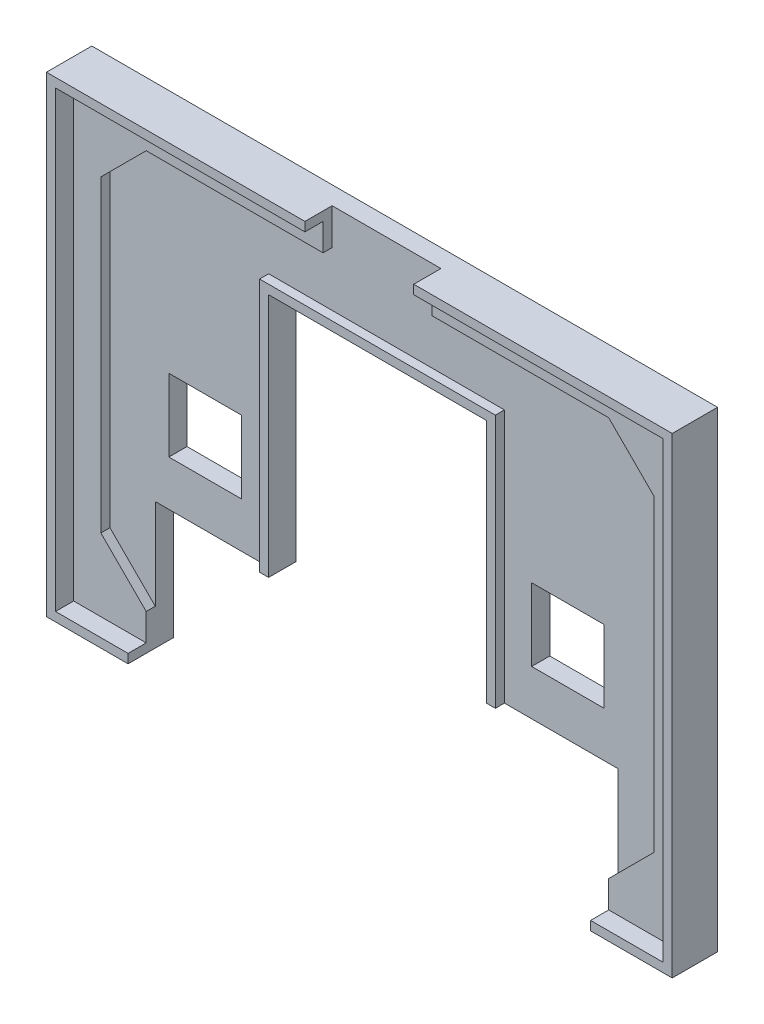
SolidWorks part; units mm, degrees
ref_plane "Přední rovina" through (0, 0, 0) normal (0, 0, 1) x (1, 0, 0)
ref_plane "Horní rovina" through (0, 0, 0) normal (0, 1, 0) x (1, 0, 0)
ref_plane "Pravá rovina" through (0, 0, 0) normal (1, 0, 0) x (0, 0, -1)
sketch "Skica1" plane through (0, 0, 0) normal (0, 0, 1) x (1, 0, 0)
  line L1 (-33.5, -25) -> (33.5, -25)
  line L2 (-33.5, -25) -> (-33.5, 25)
  line L3 (-33.5, 25) -> (33.5, 25)
  line L4 (33.5, -25) -> (33.5, 25)
  line L5 (-33.5, -25) -> (33.5, 25) construction
  line L6 (-33.5, 25) -> (33.5, -25) construction
  point P0 (0, 0)
  dimension "D1" = 67
  dimension "D2" = 50
extrude "Přidat vysunutím1" add sketch "Skica1" along normal blind 3
sketch "Skica2" plane through (0, 0, 3) normal (0, 0, 1) x (1, 0, 0)
  line L0 (-1000, 0) -> (49000, 0) construction
  line L1 (0, -1000) -> (0, 49000) construction
  line L2 (-1000, -22) -> (49000, -22) construction
  line L3 (-25.5, -1000) -> (-25.5, 49000) construction
  line L4 (-30.5, -1000) -> (-30.5, 49000) construction
  line L6 (-33.5, -25) -> (33.5, -25) construction
  line L7 (-25.5, -22) -> (-30.5, -17)
  line L8 (-30.5, -17) -> (-30.5, 17)
  line L9 (-25.5, -22) -> (25.5, -22)
  line L10 (30.5, -17) -> (30.5, 17)
  line L11 (25.5, -22) -> (30.5, -17)
  line L12 (25.5, 22) -> (30.5, 17)
  line L13 (-25.5, 22) -> (25.5, 22)
  line L14 (-25.5, 22) -> (-30.5, 17)
  point P20 (0, -22)
  point P21 (30.5, 0)
  point P24 (-30.5, 0)
  dimension "D1" = 30.5
  dimension "D2" = 5
  dimension "D3" = 3
  dimension "D4" = 45
extrude "Odebrat vysunutím1" cut sketch "Skica2" against normal offset from surface (1 mm away) 2 up to face at (0, 0, 0)
sketch "Skica3" plane through (0, 0, 0) normal (0, 0, -1) x (-1, 0, 0)
  line L0 (0, -1000) -> (0, 49000) construction
  line L1 (33.5, -25) -> (-33.5, -25) construction
  line L2 (24, 1) -> (16, 1)
  line L3 (24, 1) -> (24, -7)
  line L4 (24, -7) -> (16, -7)
  line L5 (16, 1) -> (16, -7)
  line L6 (-16, 1) -> (-16, -7)
  line L7 (33.5, -25) -> (-33.5, -25) construction
  line L8 (25.5, -25) -> (-25.5, -25)
  line L9 (25.5, -25) -> (25.5, -12)
  line L11 (-25.5, -25) -> (-25.5, -12)
  line L12 (-24, -7) -> (-16, -7)
  line L13 (25.5, -12) -> (12, -12)
  line L15 (12, -12) -> (12, 15)
  line L16 (12, 15) -> (-12, 15)
  line L17 (-12, -12) -> (-12, 15)
  line L18 (-12, -12) -> (-25.5, -12)
  line L19 (-24, 1) -> (-24, -7)
  line L20 (-24, 1) -> (-16, 1)
  dimension "D1" = 16
  dimension "D2" = 8
  dimension "D3" = 18
  dimension "D4" = 13
  dimension "D5" = 51
  dimension "D6" = 24
  dimension "D7" = 27
extrude "Odebrat vysunutím2" cut sketch "Skica3" against normal through all
sketch "Skica4" plane through (0, 0, 2) normal (0, 0, 1) x (1, 0, 0)
  line L0 (12, 15) -> (12, -12) construction
  line L1 (-12, -12) -> (-12, 15) construction
  line L2 (-12, 15) -> (12, 15) construction
  line L3 (12, 15) -> (12, -12)
  line L4 (-12, -12) -> (-12, 15)
  line L5 (-12, 15) -> (12, 15)
extrude "Vysunout tenkostěnný1" add sketch "Skica4" along normal up to surface (1 mm away) thin up to face at (0, -3.5714, 3) thin type one direction reverse wall 1
sketch "Skica5" plane through (0, 0, 0) normal (0, 0, -1) x (-1, 0, 0)
  line L0 (-33.5, 25) -> (33.5, 25) construction
  line L1 (33.5, 25) -> (33.5, -25) construction
  line L2 (33.5, -25) -> (25.5, -25) construction
  line L3 (-33.5, -25) -> (-33.5, 25) construction
  line L4 (-25.5, -25) -> (-33.5, -25) construction
  line L5 (-33.5, 25) -> (33.5, 25)
  line L6 (33.5, 25) -> (33.5, -25)
  line L7 (33.5, -25) -> (25.5, -25)
  line L8 (-33.5, -25) -> (-33.5, 25)
  line L9 (-25.5, -25) -> (-33.5, -25)
extrude "Vysunout tenkostěnný2" add sketch "Skica5" against normal blind 5 thin thin type one direction reverse wall 1
sketch "Skica6" plane through (0, 0, 2) normal (0, 0, 1) x (1, 0, 0)
  line L0 (0, -1000) -> (0, 49000) construction
  line L1 (25.5, 22) -> (-25.5, 22) construction
  line L2 (-6, 22) -> (6, 22)
  line L3 (-6, 22) -> (-6, 26)
  line L4 (-6, 26) -> (6, 26)
  line L5 (6, 22) -> (6, 26)
  line L6 (34.5, 26) -> (-34.5, 26) construction
  dimension "D1" = 12
extrude "Odebrat vysunutím3" cut sketch "Skica6" along normal through all
sketch "Skica7" plane through (0, 0, 0) normal (0, 0, -1) x (-1, 0, 0)
  line L0 (-28.7206, 22.0746) -> (-27.2752, 22.0746)
  line L1 (-27.2752, 22.0746) -> (-27.2752, 20.7289)
  line L2 (-27.2752, 20.7289) -> (-25.9793, 20.7289)
  line L3 (-25.9793, 20.7289) -> (-25.9793, 19.4331)
  line L4 (-25.9793, 19.4331) -> (-24.5589, 19.4331)
  line L5 (-24.5589, 19.4331) -> (-24.5589, 18.0625)
  line L6 (-24.5589, 18.0625) -> (-21.8924, 18.0625)
  line L7 (-21.8924, 18.0625) -> (-21.8924, 19.4331)
  line L8 (-21.8924, 19.4331) -> (-20.3972, 19.4331)
  line L9 (-20.3972, 19.4331) -> (-20.3972, 20.7289)
  line L10 (-20.3972, 20.7289) -> (-19.1262, 20.7289)
  line L11 (-19.1262, 20.7289) -> (-19.1262, 22.0746)
  line L12 (-19.1262, 22.0746) -> (-17.7556, 22.0746)
  line L13 (-17.7556, 22.0746) -> (-17.7556, 19.4331)
  line L14 (-17.7556, 19.4331) -> (-19.1262, 19.4331)
  line L15 (-19.1262, 19.4331) -> (-19.1262, 18.0625)
  line L16 (-19.1262, 18.0625) -> (-16.4597, 18.0625)
  line L17 (-16.4597, 18.0625) -> (-16.4597, 19.4331)
  line L18 (-16.4597, 19.4331) -> (-15.0642, 19.4331)
  line L19 (-15.0642, 19.4331) -> (-15.0642, 20.7539)
  line L20 (-15.0642, 20.7539) -> (-13.7185, 20.7539)
  line L21 (-13.7185, 20.7539) -> (-13.7185, 18.0625)
  line L22 (-13.7185, 18.0625) -> (-15.0642, 18.0625)
  line L23 (-15.0642, 18.0625) -> (-15.0642, 16.7168)
  line L24 (-15.0642, 16.7168) -> (-16.4597, 16.7168)
  line L25 (-16.4597, 16.7168) -> (-16.4597, 15.371)
  line L26 (-16.4597, 15.371) -> (-17.793, 15.371)
  line L27 (-17.793, 15.371) -> (-17.793, 12.555)
  line L28 (-17.793, 12.555) -> (-16.4597, 12.555)
  line L29 (-16.4597, 12.555) -> (-16.4597, 13.963)
  line L30 (-16.4597, 13.963) -> (-15.0642, 13.963)
  line L31 (-15.0642, 13.963) -> (-15.0642, 15.371)
  line L32 (-15.0642, 15.371) -> (-13.7185, 15.371)
  line L33 (-13.7185, 15.371) -> (-13.7185, 12.555)
  line L34 (-13.7185, 12.555) -> (-15.0642, 12.555)
  line L35 (-15.0642, 12.555) -> (-15.0642, 11.2592)
  line L36 (-15.0642, 11.2592) -> (-31.412, 11.2592)
  line L37 (-31.412, 11.2592) -> (-31.412, 12.555)
  line L38 (-31.412, 12.555) -> (-32.7832, 12.555)
  line L39 (-32.7832, 12.555) -> (-32.7832, 15.371)
  line L40 (-32.7832, 15.371) -> (-31.412, 15.371)
  line L41 (-31.412, 15.371) -> (-31.412, 13.963)
  line L42 (-31.412, 13.963) -> (-30.0952, 13.963)
  line L43 (-30.0952, 13.963) -> (-30.0952, 12.555)
  line L44 (-30.0952, 12.555) -> (-28.7206, 12.555)
  line L45 (-28.7206, 12.555) -> (-28.7206, 15.371)
  line L46 (-28.7206, 15.371) -> (-30.0952, 15.371)
  line L47 (-30.0952, 15.371) -> (-30.0952, 16.7168)
  line L48 (-30.0952, 16.7168) -> (-31.412, 16.7168)
  line L49 (-31.412, 16.7168) -> (-31.412, 18.0625)
  line L50 (-31.412, 18.0625) -> (-32.7832, 18.0625)
  line L51 (-32.7832, 18.0625) -> (-32.7832, 20.7289)
  line L52 (-32.7832, 20.7289) -> (-31.412, 20.7289)
  line L53 (-31.412, 20.7289) -> (-31.412, 19.3957)
  line L54 (-31.412, 19.3957) -> (-30.0952, 19.3957)
  line L55 (-30.0952, 19.3957) -> (-30.0952, 18.0625)
  line L56 (-30.0952, 18.0625) -> (-27.2752, 18.0625)
  line L57 (-27.2752, 18.0625) -> (-27.2752, 19.4331)
  line L58 (-27.2752, 19.4331) -> (-28.6852, 19.4331)
  line L59 (-28.6852, 19.4331) -> (-28.7206, 22.0746)
  line L60 (34.5, 26) -> (34.5, -26) construction
  line L61 (34.5, -26) -> (25.5, -26) construction
  line L62 (0, 0) -> (0, 37.4592) construction
  line L63 (27.2752, 19.4331) -> (28.6852, 19.4331)
  line L64 (27.2752, 18.0625) -> (27.2752, 19.4331)
  line L65 (30.0952, 18.0625) -> (27.2752, 18.0625)
  line L66 (30.0952, 19.3957) -> (30.0952, 18.0625)
  line L67 (31.412, 19.3957) -> (30.0952, 19.3957)
  line L68 (31.412, 20.7289) -> (31.412, 19.3957)
  line L69 (32.7832, 20.7289) -> (31.412, 20.7289)
  line L70 (32.7832, 18.0625) -> (32.7832, 20.7289)
  line L71 (31.412, 18.0625) -> (32.7832, 18.0625)
  line L72 (31.412, 16.7168) -> (31.412, 18.0625)
  line L73 (30.0952, 16.7168) -> (31.412, 16.7168)
  line L74 (30.0952, 15.371) -> (30.0952, 16.7168)
  line L75 (28.7206, 15.371) -> (30.0952, 15.371)
  line L76 (28.7206, 12.555) -> (28.7206, 15.371)
  line L77 (30.0952, 12.555) -> (28.7206, 12.555)
  line L78 (30.0952, 13.963) -> (30.0952, 12.555)
  line L79 (31.412, 13.963) -> (30.0952, 13.963)
  line L80 (31.412, 15.371) -> (31.412, 13.963)
  line L81 (32.7832, 15.371) -> (31.412, 15.371)
  line L82 (32.7832, 12.555) -> (32.7832, 15.371)
  line L83 (31.412, 12.555) -> (32.7832, 12.555)
  line L84 (31.412, 11.2592) -> (31.412, 12.555)
  line L85 (15.0642, 11.2592) -> (31.412, 11.2592)
  line L86 (15.0642, 12.555) -> (15.0642, 11.2592)
  line L87 (13.7185, 12.555) -> (15.0642, 12.555)
  line L88 (13.7185, 15.371) -> (13.7185, 12.555)
  line L89 (15.0642, 15.371) -> (13.7185, 15.371)
  line L90 (15.0642, 13.963) -> (15.0642, 15.371)
  line L91 (16.4597, 13.963) -> (15.0642, 13.963)
  line L92 (16.4597, 12.555) -> (16.4597, 13.963)
  line L93 (17.793, 12.555) -> (16.4597, 12.555)
  line L94 (17.793, 15.371) -> (17.793, 12.555)
  line L95 (16.4597, 15.371) -> (17.793, 15.371)
  line L96 (16.4597, 16.7168) -> (16.4597, 15.371)
  line L97 (15.0642, 16.7168) -> (16.4597, 16.7168)
  line L98 (15.0642, 18.0625) -> (15.0642, 16.7168)
  line L99 (13.7185, 18.0625) -> (15.0642, 18.0625)
  line L100 (13.7185, 20.7539) -> (13.7185, 18.0625)
  line L101 (15.0642, 20.7539) -> (13.7185, 20.7539)
  line L102 (15.0642, 19.4331) -> (15.0642, 20.7539)
  line L103 (16.4597, 19.4331) -> (15.0642, 19.4331)
  line L104 (16.4597, 18.0625) -> (16.4597, 19.4331)
  line L105 (19.1262, 18.0625) -> (16.4597, 18.0625)
  line L106 (19.1262, 19.4331) -> (19.1262, 18.0625)
  line L107 (17.7556, 19.4331) -> (19.1262, 19.4331)
  line L108 (17.7556, 22.0746) -> (17.7556, 19.4331)
  line L109 (19.1262, 22.0746) -> (17.7556, 22.0746)
  line L110 (19.1262, 20.7289) -> (19.1262, 22.0746)
  line L111 (20.3972, 20.7289) -> (19.1262, 20.7289)
  line L112 (20.3972, 19.4331) -> (20.3972, 20.7289)
  line L113 (21.8924, 19.4331) -> (20.3972, 19.4331)
  line L114 (21.8924, 18.0625) -> (21.8924, 19.4331)
  line L115 (24.5589, 18.0625) -> (21.8924, 18.0625)
  line L116 (24.5589, 19.4331) -> (24.5589, 18.0625)
  line L117 (25.9793, 19.4331) -> (24.5589, 19.4331)
  line L118 (25.9793, 20.7289) -> (25.9793, 19.4331)
  line L119 (27.2752, 20.7289) -> (25.9793, 20.7289)
  line L120 (27.2752, 22.0746) -> (27.2752, 20.7289)
  line L121 (28.7206, 22.0746) -> (27.2752, 22.0746)
  line L122 (28.6852, 19.4331) -> (28.7206, 22.0746)
extrude "Odebrat vysunutím4" cut sketch "Skica7" against normal blind 1
sketch "Skica8" plane through (0, 0, 1) normal (0, 0, -1) x (-1, 0, 0)
  line L5 (-27.2869, 16.7813) -> (-25.9344, 16.7813)
  line L6 (-27.2869, 16.7813) -> (-27.2869, 15.3917)
  line L7 (-27.2869, 15.3917) -> (-25.9344, 15.3917)
  line L9 (-25.9344, 16.7813) -> (-25.9344, 15.3917)
  line L12 (-20.4943, 16.7813) -> (-19.1262, 16.7813)
  line L14 (-20.4943, 16.7813) -> (-20.4943, 15.3917)
  line L15 (-20.4943, 15.3917) -> (-19.1262, 15.3917)
  line L16 (-19.1262, 16.7813) -> (-19.1262, 15.3917)
  line L23 (0, 0) -> (0, 37.0283) construction
  line L24 (20.4943, 15.3917) -> (19.1262, 15.3917)
  line L25 (19.1262, 16.7813) -> (19.1262, 15.3917)
  line L26 (20.4943, 16.7813) -> (19.1262, 16.7813)
  line L27 (20.4943, 16.7813) -> (20.4943, 15.3917)
  line L32 (24.5589, 12.555) -> (21.8924, 12.555)
  line L33 (21.8924, 13.905) -> (21.8924, 12.555)
  line L38 (-24.5589, 13.905) -> (-21.8924, 13.905)
  line L39 (-24.5589, 13.905) -> (-24.5589, 12.555)
  line L40 (-24.5589, 12.555) -> (-21.8924, 12.555)
  line L41 (-21.8924, 13.905) -> (-21.8924, 12.555)
  line L42 (24.5589, 13.905) -> (21.8924, 13.905)
  line L43 (24.5589, 13.905) -> (24.5589, 12.555)
  line L44 (27.2869, 15.3917) -> (25.9344, 15.3917)
  line L45 (25.9344, 16.7813) -> (25.9344, 15.3917)
  line L46 (27.2869, 16.7813) -> (25.9344, 16.7813)
  line L47 (27.2869, 16.7813) -> (27.2869, 15.3917)
extrude "Přidat vysunutím3" add sketch "Skica8" along normal blind 1
sketch "Skica10" plane through (0, 0, 0) normal (0, 0, -1) x (-1, 0, 0)
  text T0 "AXOL" font "BLOXAT" height 5.8
extrude "Odebrat vysunutím5" cut sketch "Skica10" against normal blind 1
